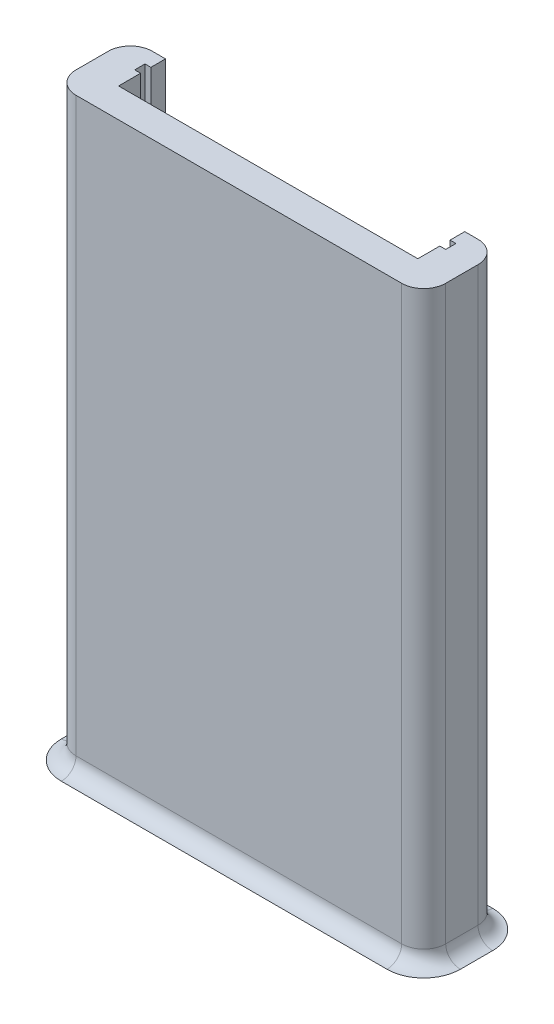
SolidWorks part; units mm, degrees
material "Melamine resin"
ref_plane "Front Plane" through (0, 0, 0) normal (0, 0, 1) x (1, 0, 0)
ref_plane "Top Plane" through (0, 0, 0) normal (0, 1, 0) x (1, 0, 0)
ref_plane "Right Plane" through (0, 0, 0) normal (1, 0, 0) x (0, 0, -1)
sketch "Sketch2" plane through (0, 0, 0) normal (0, 1, 0) x (1, 0, 0)
  line L1 (0, 0) -> (88.9, 0)
  line L2 (0, 0) -> (0, 152.4)
  line L3 (0, 152.4) -> (88.9, 152.4)
  line L10 (88.9, 152.4) -> (88.9, 0)
  dimension "D1" = 152.4
  dimension "D2" = 88.9
extrude "Boss-Extrude1" add sketch "Sketch2" along normal blind 5.9944 contours L3 L10 L1 L2
sketch "Sketch4" plane through (0, 5.9944, 0) normal (0, 1, 0) x (1, 0, 0)
  line L0 (0, 0) -> (0, 152.4) construction
  line L1 (0, 0) -> (88.9, 0) construction
  circle A0 centre (45.72, 109.8713) radius 2.7305
  circle A1 centre (45.72, 33.6713) radius 2.7305
  dimension "D3" = 5.461
  dimension "D4" = 5.461
  dimension "D1" = 76.2
  dimension "D2" = 45.72
  dimension "D5" = 33.6713
extrude "Cut-Extrude2" cut sketch "Sketch4" against normal through all both
sketch "Sketch5" plane through (0, 5.9944, 0) normal (0, 1, 0) x (1, 0, 0)
  line L0 (0, 152.4) -> (88.9, 152.4) construction
  line L1 (12.446, 15.748) -> (76.454, 15.748)
  line L2 (12.446, 15.748) -> (12.446, 2.54)
  line L3 (12.446, 2.54) -> (76.454, 2.54)
  line L4 (76.454, 15.748) -> (76.454, 2.54)
  line L5 (18.542, 7.62) -> (70.358, 7.62)
  line L6 (18.542, 7.62) -> (18.542, 15.748)
  line L7 (18.542, 15.748) -> (70.358, 15.748)
  line L8 (70.358, 7.62) -> (70.358, 15.748)
  line L9 (17.526, 13.208) -> (71.374, 13.208)
  line L10 (17.526, 13.208) -> (17.526, 11.43)
  line L11 (17.526, 11.43) -> (71.374, 11.43)
  line L12 (71.374, 13.208) -> (71.374, 11.43)
  line L13 (0, 0) -> (88.9, 0) construction
  point P16 (44.45, 152.4)
  point P17 (44.45, 15.748)
  dimension "D1" = 53.848
  dimension "D2" = 1.016
  dimension "D3" = 1.016
  dimension "D4" = 3.81
  dimension "D5" = 2.54
  dimension "D6" = 5.08
  dimension "D7" = 5.08
  dimension "D8" = 1.778
  dimension "D9" = 2.54
  dimension "D10" = 5.08
extrude "Boss-Extrude2" add sketch "Sketch5" along normal blind 101.6 contours L9 L12 L11 L8 L5 L6 L10 L1 L2 L3 L4 region at (44.45, 5.9944, -6.5736)
fillet "Fillet1" radius 3.81 4 edges at (12.446, 56.7944, -2.54) (12.446, 56.7944, -15.748) (76.454, 56.7944, -2.54) (76.454, 56.7944, -15.748)
fillet "Fillet2" radius 2.54 9 edges at (17.399, 5.9944, -15.748) (13.5619, 5.9944, -14.6321) (12.446, 5.9944, -9.144) (13.5619, 5.9944, -3.6559) (71.501, 5.9944, -15.748) (75.3381, 5.9944, -14.6321) (76.454, 5.9944, -9.144) (75.3381, 5.9944, -3.6559) (44.45, 5.9944, -2.54)
ref_plane "Plane1" through (44.45, 0, 0) normal (-1, 0, 0) x (0, 0, 1)
sketch "Sketch6" plane through (44.45, 0, 0) normal (-1, 0, 0) x (0, 0, 1)
  line L0 (0, 5.9944) -> (-152.4, 5.9944) construction
  line L1 (0, 5.9944) -> (-152.4, 5.9944)
  line L3 (-149.86, 5.9944) -> (-79.121, 5.9944)
  line L4 (-149.86, 5.9944) -> (-149.86, 23.1394)
  line L5 (-149.86, 23.1394) -> (-79.121, 23.1394)
  line L6 (-79.121, 5.9944) -> (-79.121, 23.1394)
  line L7 (-142.875, 23.1394) -> (-86.106, 23.1394)
  line L8 (-142.875, 23.1394) -> (-142.875, 11.0744)
  line L9 (-142.875, 11.0744) -> (-86.106, 11.0744)
  line L10 (-86.106, 23.1394) -> (-86.106, 11.0744)
  line L11 (-144.78, 18.0594) -> (-84.201, 18.0594)
  line L12 (-144.78, 18.0594) -> (-144.78, 16.1544)
  line L13 (-144.78, 16.1544) -> (-84.201, 16.1544)
  line L14 (-84.201, 18.0594) -> (-84.201, 16.1544)
  line L15 (-152.4, 5.9944) -> (-152.4, 0) construction
  dimension "D1" = 60.579
  dimension "D2" = 1.905
  dimension "D3" = 1.905
  dimension "D4" = 1.905
  dimension "D5" = 5.08
  dimension "D6" = 5.08
  dimension "D7" = 5.08
  dimension "D8" = 5.08
  dimension "D9" = 5.08
  dimension "D10" = 2.54
extrude "Boss-Extrude3" add sketch "Sketch6" along normal mid plane 40.64 contours L11 L14 L13 L10 L9 L8 L12 L5 L4 L1 L6 region at (44.45, 6.7223, -114.4905)
fillet "Fillet3" radius 3.81 2 edges at (44.45, 23.1394, -79.121) (44.45, 23.1394, -149.86)
fillet "Fillet6" radius 3.81 12 edges at (24.13, 23.1394, -84.5185) (24.13, 22.0235, -80.2369) (64.77, 23.1394, -84.5185) (64.77, 22.0235, -80.2369) (64.77, 23.1394, -144.4625) (64.77, 22.0235, -148.7441) (24.13, 23.1394, -144.4625) (24.13, 22.0235, -148.7441) (24.13, 12.6619, -79.121) (64.77, 12.6619, -79.121) (64.77, 12.6619, -149.86) (24.13, 12.6619, -149.86)
fillet "Fillet7" radius 2.54 8 edges at (25.2459, 5.9944, -80.2369) (44.45, 5.9944, -79.121) (63.6541, 5.9944, -80.2369) (64.77, 5.9944, -114.4905) (63.6541, 5.9944, -148.7441) (44.45, 5.9944, -149.86) (25.2459, 5.9944, -148.7441) (24.13, 5.9944, -114.4905)
sketch "Sketch7" plane through (0, 5.9944, 0) normal (0, 1, 0) x (1, 0, 0)
  line L0 (0, 0) -> (16.256, 0) construction
  line L1 (0, 152.4) -> (2.54, 152.4)
  line L2 (0, 152.4) -> (0, 0)
  line L3 (0, 0) -> (2.54, 0)
  line L4 (2.54, 152.4) -> (2.54, 0)
  dimension "D1" = 2.54
extrude "Cut-Extrude3" cut sketch "Sketch7" against normal through all both
sketch "Sketch8" plane through (0, 0, 0) normal (0, -1, 0) x (1, 0, 0)
  line L4 (2.54, 0) -> (2.54, -152.4)
  line L5 (2.54, -152.4) -> (88.9, -152.4)
  line L6 (88.9, -152.4) -> (88.9, 0)
  line L7 (88.9, 0) -> (2.54, 0)
  line L8 (2.54, 0) -> (2.54, -152.4)
  line L9 (2.54, -152.4) -> (88.9, -152.4)
  line L10 (88.9, -152.4) -> (88.9, 0)
  line L11 (88.9, 0) -> (2.54, 0)
  dimension "D1" = 0
extrude "Cut-Extrude5" cut sketch "Sketch8" against normal up to surface (5.9944 mm away) up to face at (44.6087, 5.9944, -45.1326)
sketch "Sketch9" plane through (0, 5.9944, 0) normal (0, -1, 0) x (1, 0, 0)
  line L0 (44.45, -2.54) -> (44.45, -7.62) construction
  line L1 (16.256, -2.54) -> (72.644, -2.54) construction
  line L2 (18.542, -7.62) -> (70.358, -7.62) construction
  line L3 (69.85, -5.08) -> (44.45, -5.08) construction
  line L4 (44.45, -5.08) -> (19.05, -5.08) construction
  circle A0 centre (69.85, -5.08) radius 0.7937
  circle A1 centre (19.05, -5.08) radius 0.7937
  point P4 (44.45, -5.08)
  dimension "D2" = 1.5875
  dimension "D1" = 50.8
extrude "Cut-Extrude6" cut sketch "Sketch9" against normal blind 3.175
equation "\"threaded_insert_hole\"=0.1472"
equation "\"th\"=1.25249"
